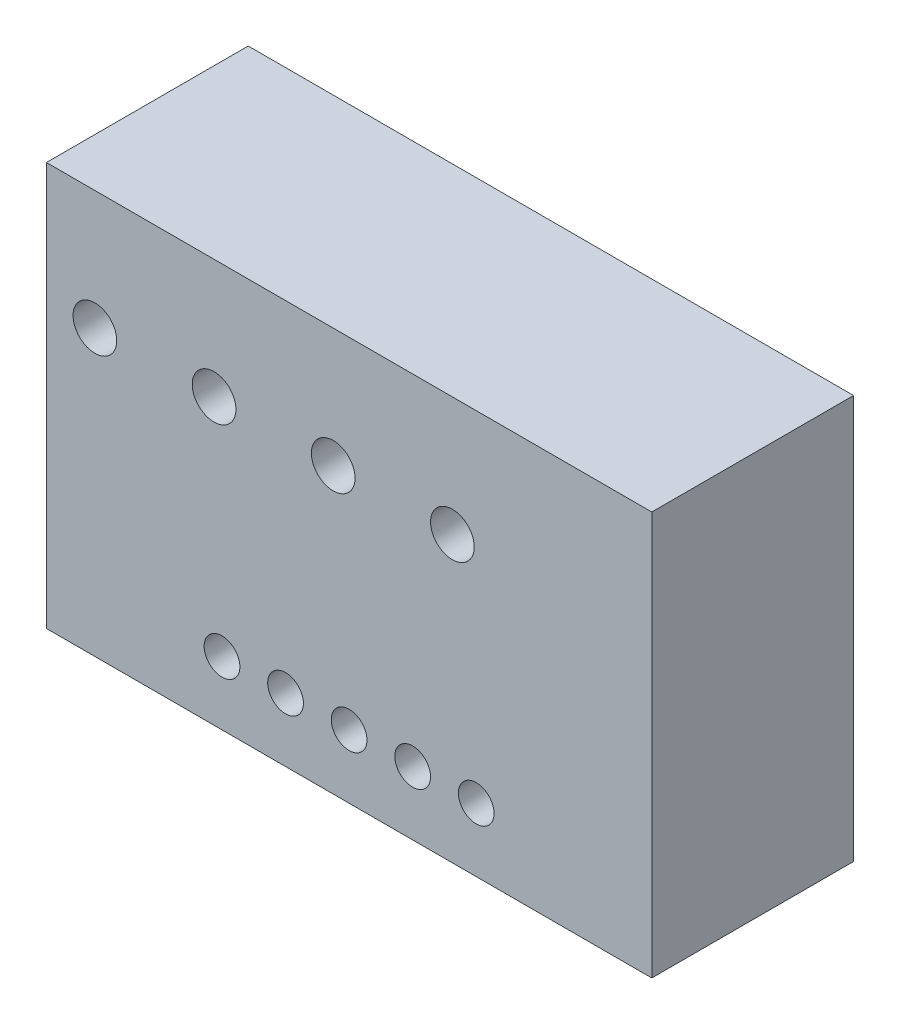
SolidWorks part; units mm, degrees
ref_plane "Front Plane" through (0, 0, 0) normal (0, 0, 1) x (1, 0, 0)
ref_plane "Top Plane" through (0, 0, 0) normal (0, 1, 0) x (1, 0, 0)
ref_plane "Right Plane" through (0, 0, 0) normal (1, 0, 0) x (0, 0, -1)
sketch "Sketch1" plane through (0, 0, 0) normal (0, 0, 1) x (1, 0, 0)
  line L1 (38.1, -25.4) -> (-38.1, -25.4)
  line L2 (38.1, -25.4) -> (38.1, 25.4)
  line L3 (38.1, 25.4) -> (-38.1, 25.4)
  line L4 (-38.1, -25.4) -> (-38.1, 25.4)
  line L5 (38.1, -25.4) -> (-38.1, 25.4) construction
  line L6 (38.1, 25.4) -> (-38.1, -25.4) construction
  point P0 (0, 0)
  point P6 (-8, -17.4)
  point P7 (-16, -17.4)
  point P8 (0, -17.4)
  point P9 (8, -17.4)
  point P10 (16, -17.4)
  point P11 (-17, 10.4)
  point P12 (-2, 10.4)
  point P13 (13, 10.4)
  point P14 (-32, 10.4)
  point P15 (0, 0)
  point P16 (-13.9836, 10.4)
  dimension "D1" = 50.8
  dimension "D2" = 76.2
  dimension "D3" = 8
  dimension "D4" = 8
  dimension "D5" = 8
  dimension "D6" = 8
  dimension "D7" = 8
  dimension "D8" = 15
  dimension "D9" = 15
  dimension "D10" = 15
  dimension "D11" = 15
  dimension "D12" = 16
extrude "Boss-Extrude1" add sketch "Sketch1" along normal blind 25.4
hole_wizard "M4 Clearance Hole1" positions "Sketch2" profile "Sketch3" hole size "M4" standard "ANSI Metric" end condition through all
sketch "Sketch2" plane through (0, 0, 25.4) normal (0, 0, 1) x (1, 0, 0)
  point P0 (-16, -17.4)
  point P3 (-8, -17.4)
  point P6 (0, -17.4)
  point P9 (8, -17.4)
  point P12 (16, -17.4)
sketch "Sketch3" plane through (-16, -17.4, 25.4) normal (1, 0, 0) x (0, -1, 0)
  line L0 (0, 0) -> (0, 25.4)
  line L1 (0, 25.4) -> (2.25, 25.4)
  line L2 (2.25, 25.4) -> (2.25, 0)
  line L5 (2.25, 0) -> (0, 0)
  line L11 (0, -6.35) -> (0, 107.95) construction
  dimension "Thru Hole Dia." = 4.5
  dimension "Thru Hole Depth" = 25.4
hole_wizard "M5 Clearance Hole1" positions "Sketch4" profile "Sketch5" hole size "M5" standard "ANSI Metric" end condition through all
sketch "Sketch4" plane through (0, 0, 25.4) normal (0, 0, 1) x (1, 0, 0)
  point P0 (-32, 10.4)
  point P3 (-17, 10.4)
  point P6 (-2, 10.4)
  point P9 (13, 10.4)
sketch "Sketch5" plane through (-32, 10.4, 25.4) normal (1, 0, 0) x (0, -1, 0)
  line L0 (0, 0) -> (0, 25.4)
  line L1 (0, 25.4) -> (2.75, 25.4)
  line L2 (2.75, 25.4) -> (2.75, 0)
  line L5 (2.75, 0) -> (0, 0)
  line L11 (0, -6.35) -> (0, 107.95) construction
  dimension "Thru Hole Dia." = 5.5
  dimension "Thru Hole Depth" = 25.4
